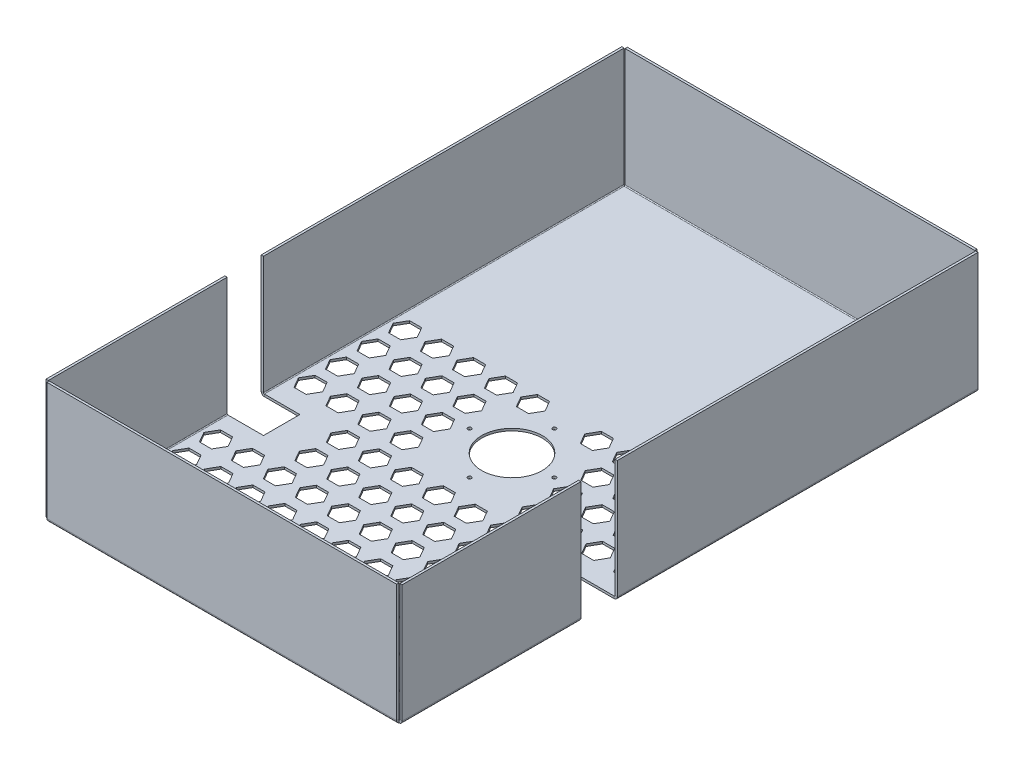
SolidWorks part; units mm, degrees
note: The reader was unsure of these and kept them because the rebuilt part matched: flange length of "Brida de arista1", "Brida de arista2".
ref_plane "Alzado" through (0, 0, 0) normal (0, 0, 1) x (1, 0, 0)
ref_plane "Planta" through (0, 0, 0) normal (0, 1, 0) x (1, 0, 0)
ref_plane "Vista lateral" through (0, 0, 0) normal (1, 0, 0) x (0, 0, -1)
sketch "Croquis1" plane through (0, 0, 0) normal (0, 1, 0) x (1, 0, 0)
  line L0 (-145, -75) -> (-115, -75) construction
  line L1 (-145, 237.5) -> (145, 237.5)
  line L2 (-145, 237.5) -> (-145, -60)
  line L3 (-145, -237.5) -> (145, -237.5)
  line L4 (145, 237.5) -> (145, -60)
  line L5 (-145, 237.5) -> (145, -237.5) construction
  line L6 (-145, -237.5) -> (145, 237.5) construction
  line L7 (0, 35) -> (0, 0) construction
  line L8 (0, 0) -> (-35, 0) construction
  line L9 (-115, -90) -> (-115, -60)
  line L10 (-115, -60) -> (-145, -60)
  line L11 (-115, -90) -> (-145, -90)
  line L12 (-145, -90) -> (-145, -237.5)
  line L13 (115, -90) -> (145, -90)
  line L14 (115, -90) -> (115, -60)
  line L15 (115, -60) -> (145, -60)
  line L16 (145, -90) -> (145, -237.5)
  line L17 (-145, 225.66) -> (-118.6364, 225.66) construction
  line L18 (-118.6364, 225.66) -> (-92.2727, 225.66) construction
  line L19 (-92.2727, 225.66) -> (-65.9091, 225.66) construction
  line L20 (-65.9091, 225.66) -> (-39.5455, 225.66) construction
  line L21 (-39.5455, 225.66) -> (-13.1818, 225.66) construction
  line L22 (-13.1818, 225.66) -> (13.1818, 225.66) construction
  line L23 (13.1818, 225.66) -> (39.5455, 225.66) construction
  line L24 (39.5455, 225.66) -> (65.9091, 225.66) construction
  line L25 (65.9091, 225.66) -> (92.2727, 225.66) construction
  line L26 (92.2727, 225.66) -> (118.6364, 225.66) construction
  line L27 (118.6364, 225.66) -> (145, 225.66) construction
  line L490 (-121.8182, 43.66) -> (-126.8182, 52.3203)
  line L491 (-126.8182, 52.3203) -> (-136.8182, 52.3203)
  line L492 (-136.8182, 52.3203) -> (-141.8182, 43.66)
  line L493 (-141.8182, 43.66) -> (-136.8182, 34.9997)
  line L494 (-136.8182, 34.9997) -> (-126.8182, 34.9997)
  line L495 (-126.8182, 34.9997) -> (-121.8182, 43.66)
  line L496 (-95.4582, 43.66) -> (-100.4582, 52.3203)
  line L497 (-100.4582, 52.3203) -> (-110.4582, 52.3203)
  line L498 (-110.4582, 52.3203) -> (-115.4582, 43.66)
  line L499 (-115.4582, 43.66) -> (-110.4582, 34.9997)
  line L500 (-110.4582, 34.9997) -> (-100.4582, 34.9997)
  line L501 (-100.4582, 34.9997) -> (-95.4582, 43.66)
  line L502 (-69.0982, 43.66) -> (-74.0982, 52.3203)
  line L503 (-74.0982, 52.3203) -> (-84.0982, 52.3203)
  line L504 (-84.0982, 52.3203) -> (-89.0982, 43.66)
  line L505 (-89.0982, 43.66) -> (-84.0982, 34.9997)
  line L506 (-84.0982, 34.9997) -> (-74.0982, 34.9997)
  line L507 (-74.0982, 34.9997) -> (-69.0982, 43.66)
  line L508 (-42.7382, 43.66) -> (-47.7382, 52.3203)
  line L509 (-47.7382, 52.3203) -> (-57.7382, 52.3203)
  line L510 (-57.7382, 52.3203) -> (-62.7382, 43.66)
  line L511 (-62.7382, 43.66) -> (-57.7382, 34.9997)
  line L512 (-57.7382, 34.9997) -> (-47.7382, 34.9997)
  line L513 (-47.7382, 34.9997) -> (-42.7382, 43.66)
  line L514 (-16.3782, 43.66) -> (-21.3782, 52.3203)
  line L515 (-21.3782, 52.3203) -> (-31.3782, 52.3203)
  line L516 (-31.3782, 52.3203) -> (-36.3782, 43.66)
  line L517 (-36.3782, 43.66) -> (-31.3782, 34.9997)
  line L518 (-31.3782, 34.9997) -> (-21.3782, 34.9997)
  line L519 (-21.3782, 34.9997) -> (-16.3782, 43.66)
  line L526 (36.3418, 43.66) -> (31.3418, 52.3203)
  line L527 (31.3418, 52.3203) -> (21.3418, 52.3203)
  line L528 (21.3418, 52.3203) -> (16.3418, 43.66)
  line L529 (16.3418, 43.66) -> (21.3418, 34.9997)
  line L530 (21.3418, 34.9997) -> (31.3418, 34.9997)
  line L531 (31.3418, 34.9997) -> (36.3418, 43.66)
  line L532 (62.7018, 43.66) -> (57.7018, 52.3203)
  line L533 (57.7018, 52.3203) -> (47.7018, 52.3203)
  line L534 (47.7018, 52.3203) -> (42.7018, 43.66)
  line L535 (42.7018, 43.66) -> (47.7018, 34.9997)
  line L536 (47.7018, 34.9997) -> (57.7018, 34.9997)
  line L537 (57.7018, 34.9997) -> (62.7018, 43.66)
  line L538 (89.0618, 43.66) -> (84.0618, 52.3203)
  line L539 (84.0618, 52.3203) -> (74.0618, 52.3203)
  line L540 (74.0618, 52.3203) -> (69.0618, 43.66)
  line L541 (69.0618, 43.66) -> (74.0618, 34.9997)
  line L542 (74.0618, 34.9997) -> (84.0618, 34.9997)
  line L543 (84.0618, 34.9997) -> (89.0618, 43.66)
  line L544 (115.4218, 43.66) -> (110.4218, 52.3203)
  line L545 (110.4218, 52.3203) -> (100.4218, 52.3203)
  line L546 (100.4218, 52.3203) -> (95.4218, 43.66)
  line L547 (95.4218, 43.66) -> (100.4218, 34.9997)
  line L548 (100.4218, 34.9997) -> (110.4218, 34.9997)
  line L549 (110.4218, 34.9997) -> (115.4218, 43.66)
  line L550 (141.7818, 43.66) -> (136.7818, 52.3203)
  line L551 (136.7818, 52.3203) -> (126.7818, 52.3203)
  line L552 (126.7818, 52.3203) -> (121.7818, 43.66)
  line L553 (121.7818, 43.66) -> (126.7818, 34.9997)
  line L554 (126.7818, 34.9997) -> (136.7818, 34.9997)
  line L555 (136.7818, 34.9997) -> (141.7818, 43.66)
  line L556 (-121.8182, 17.66) -> (-126.8182, 26.3203)
  line L557 (-126.8182, 26.3203) -> (-136.8182, 26.3203)
  line L558 (-136.8182, 26.3203) -> (-141.8182, 17.66)
  line L559 (-141.8182, 17.66) -> (-136.8182, 8.9997)
  line L560 (-136.8182, 8.9997) -> (-126.8182, 8.9997)
  line L561 (-126.8182, 8.9997) -> (-121.8182, 17.66)
  line L562 (-95.4582, 17.66) -> (-100.4582, 26.3203)
  line L563 (-100.4582, 26.3203) -> (-110.4582, 26.3203)
  line L564 (-110.4582, 26.3203) -> (-115.4582, 17.66)
  line L565 (-115.4582, 17.66) -> (-110.4582, 8.9997)
  line L566 (-110.4582, 8.9997) -> (-100.4582, 8.9997)
  line L567 (-100.4582, 8.9997) -> (-95.4582, 17.66)
  line L568 (-69.0982, 17.66) -> (-74.0982, 26.3203)
  line L569 (-74.0982, 26.3203) -> (-84.0982, 26.3203)
  line L570 (-84.0982, 26.3203) -> (-89.0982, 17.66)
  line L571 (-89.0982, 17.66) -> (-84.0982, 8.9997)
  line L572 (-84.0982, 8.9997) -> (-74.0982, 8.9997)
  line L573 (-74.0982, 8.9997) -> (-69.0982, 17.66)
  line L574 (-42.7382, 17.66) -> (-47.7382, 26.3203)
  line L575 (-47.7382, 26.3203) -> (-57.7382, 26.3203)
  line L576 (-57.7382, 26.3203) -> (-62.7382, 17.66)
  line L577 (-62.7382, 17.66) -> (-57.7382, 8.9997)
  line L578 (-57.7382, 8.9997) -> (-47.7382, 8.9997)
  line L579 (-47.7382, 8.9997) -> (-42.7382, 17.66)
  line L598 (62.7018, 17.66) -> (57.7018, 26.3203)
  line L599 (57.7018, 26.3203) -> (47.7018, 26.3203)
  line L600 (47.7018, 26.3203) -> (42.7018, 17.66)
  line L601 (42.7018, 17.66) -> (47.7018, 8.9997)
  line L602 (47.7018, 8.9997) -> (57.7018, 8.9997)
  line L603 (57.7018, 8.9997) -> (62.7018, 17.66)
  line L604 (89.0618, 17.66) -> (84.0618, 26.3203)
  line L605 (84.0618, 26.3203) -> (74.0618, 26.3203)
  line L606 (74.0618, 26.3203) -> (69.0618, 17.66)
  line L607 (69.0618, 17.66) -> (74.0618, 8.9997)
  line L608 (74.0618, 8.9997) -> (84.0618, 8.9997)
  line L609 (84.0618, 8.9997) -> (89.0618, 17.66)
  line L610 (115.4218, 17.66) -> (110.4218, 26.3203)
  line L611 (110.4218, 26.3203) -> (100.4218, 26.3203)
  line L612 (100.4218, 26.3203) -> (95.4218, 17.66)
  line L613 (95.4218, 17.66) -> (100.4218, 8.9997)
  line L614 (100.4218, 8.9997) -> (110.4218, 8.9997)
  line L615 (110.4218, 8.9997) -> (115.4218, 17.66)
  line L616 (141.7818, 17.66) -> (136.7818, 26.3203)
  line L617 (136.7818, 26.3203) -> (126.7818, 26.3203)
  line L618 (126.7818, 26.3203) -> (121.7818, 17.66)
  line L619 (121.7818, 17.66) -> (126.7818, 8.9997)
  line L620 (126.7818, 8.9997) -> (136.7818, 8.9997)
  line L621 (136.7818, 8.9997) -> (141.7818, 17.66)
  line L622 (-121.8182, -8.34) -> (-126.8182, 0.3203)
  line L623 (-126.8182, 0.3203) -> (-136.8182, 0.3203)
  line L624 (-136.8182, 0.3203) -> (-141.8182, -8.34)
  line L625 (-141.8182, -8.34) -> (-136.8182, -17.0003)
  line L626 (-136.8182, -17.0003) -> (-126.8182, -17.0003)
  line L627 (-126.8182, -17.0003) -> (-121.8182, -8.34)
  line L628 (-95.4582, -8.34) -> (-100.4582, 0.3203)
  line L629 (-100.4582, 0.3203) -> (-110.4582, 0.3203)
  line L630 (-110.4582, 0.3203) -> (-115.4582, -8.34)
  line L631 (-115.4582, -8.34) -> (-110.4582, -17.0003)
  line L632 (-110.4582, -17.0003) -> (-100.4582, -17.0003)
  line L633 (-100.4582, -17.0003) -> (-95.4582, -8.34)
  line L634 (-69.0982, -8.34) -> (-74.0982, 0.3203)
  line L635 (-74.0982, 0.3203) -> (-84.0982, 0.3203)
  line L636 (-84.0982, 0.3203) -> (-89.0982, -8.34)
  line L637 (-89.0982, -8.34) -> (-84.0982, -17.0003)
  line L638 (-84.0982, -17.0003) -> (-74.0982, -17.0003)
  line L639 (-74.0982, -17.0003) -> (-69.0982, -8.34)
  line L640 (-42.7382, -8.34) -> (-47.7382, 0.3203)
  line L641 (-47.7382, 0.3203) -> (-57.7382, 0.3203)
  line L642 (-57.7382, 0.3203) -> (-62.7382, -8.34)
  line L643 (-62.7382, -8.34) -> (-57.7382, -17.0003)
  line L644 (-57.7382, -17.0003) -> (-47.7382, -17.0003)
  line L645 (-47.7382, -17.0003) -> (-42.7382, -8.34)
  line L664 (62.7018, -8.34) -> (57.7018, 0.3203)
  line L665 (57.7018, 0.3203) -> (47.7018, 0.3203)
  line L666 (47.7018, 0.3203) -> (42.7018, -8.34)
  line L667 (42.7018, -8.34) -> (47.7018, -17.0003)
  line L668 (47.7018, -17.0003) -> (57.7018, -17.0003)
  line L669 (57.7018, -17.0003) -> (62.7018, -8.34)
  line L670 (89.0618, -8.34) -> (84.0618, 0.3203)
  line L671 (84.0618, 0.3203) -> (74.0618, 0.3203)
  line L672 (74.0618, 0.3203) -> (69.0618, -8.34)
  line L673 (69.0618, -8.34) -> (74.0618, -17.0003)
  line L674 (74.0618, -17.0003) -> (84.0618, -17.0003)
  line L675 (84.0618, -17.0003) -> (89.0618, -8.34)
  line L676 (115.4218, -8.34) -> (110.4218, 0.3203)
  line L677 (110.4218, 0.3203) -> (100.4218, 0.3203)
  line L678 (100.4218, 0.3203) -> (95.4218, -8.34)
  line L679 (95.4218, -8.34) -> (100.4218, -17.0003)
  line L680 (100.4218, -17.0003) -> (110.4218, -17.0003)
  line L681 (110.4218, -17.0003) -> (115.4218, -8.34)
  line L682 (141.7818, -8.34) -> (136.7818, 0.3203)
  line L683 (136.7818, 0.3203) -> (126.7818, 0.3203)
  line L684 (126.7818, 0.3203) -> (121.7818, -8.34)
  line L685 (121.7818, -8.34) -> (126.7818, -17.0003)
  line L686 (126.7818, -17.0003) -> (136.7818, -17.0003)
  line L687 (136.7818, -17.0003) -> (141.7818, -8.34)
  line L688 (-121.8182, -34.34) -> (-126.8182, -25.6797)
  line L689 (-126.8182, -25.6797) -> (-136.8182, -25.6797)
  line L690 (-136.8182, -25.6797) -> (-141.8182, -34.34)
  line L691 (-141.8182, -34.34) -> (-136.8182, -43.0003)
  line L692 (-136.8182, -43.0003) -> (-126.8182, -43.0003)
  line L693 (-126.8182, -43.0003) -> (-121.8182, -34.34)
  line L694 (-95.4582, -34.34) -> (-100.4582, -25.6797)
  line L695 (-100.4582, -25.6797) -> (-110.4582, -25.6797)
  line L696 (-110.4582, -25.6797) -> (-115.4582, -34.34)
  line L697 (-115.4582, -34.34) -> (-110.4582, -43.0003)
  line L698 (-110.4582, -43.0003) -> (-100.4582, -43.0003)
  line L699 (-100.4582, -43.0003) -> (-95.4582, -34.34)
  line L700 (-69.0982, -34.34) -> (-74.0982, -25.6797)
  line L701 (-74.0982, -25.6797) -> (-84.0982, -25.6797)
  line L702 (-84.0982, -25.6797) -> (-89.0982, -34.34)
  line L703 (-89.0982, -34.34) -> (-84.0982, -43.0003)
  line L704 (-84.0982, -43.0003) -> (-74.0982, -43.0003)
  line L705 (-74.0982, -43.0003) -> (-69.0982, -34.34)
  line L706 (-42.7382, -34.34) -> (-47.7382, -25.6797)
  line L707 (-47.7382, -25.6797) -> (-57.7382, -25.6797)
  line L708 (-57.7382, -25.6797) -> (-62.7382, -34.34)
  line L709 (-62.7382, -34.34) -> (-57.7382, -43.0003)
  line L710 (-57.7382, -43.0003) -> (-47.7382, -43.0003)
  line L711 (-47.7382, -43.0003) -> (-42.7382, -34.34)
  line L730 (62.7018, -34.34) -> (57.7018, -25.6797)
  line L731 (57.7018, -25.6797) -> (47.7018, -25.6797)
  line L732 (47.7018, -25.6797) -> (42.7018, -34.34)
  line L733 (42.7018, -34.34) -> (47.7018, -43.0003)
  line L734 (47.7018, -43.0003) -> (57.7018, -43.0003)
  line L735 (57.7018, -43.0003) -> (62.7018, -34.34)
  line L736 (89.0618, -34.34) -> (84.0618, -25.6797)
  line L737 (84.0618, -25.6797) -> (74.0618, -25.6797)
  line L738 (74.0618, -25.6797) -> (69.0618, -34.34)
  line L739 (69.0618, -34.34) -> (74.0618, -43.0003)
  line L740 (74.0618, -43.0003) -> (84.0618, -43.0003)
  line L741 (84.0618, -43.0003) -> (89.0618, -34.34)
  line L742 (115.4218, -34.34) -> (110.4218, -25.6797)
  line L743 (110.4218, -25.6797) -> (100.4218, -25.6797)
  line L744 (100.4218, -25.6797) -> (95.4218, -34.34)
  line L745 (95.4218, -34.34) -> (100.4218, -43.0003)
  line L746 (100.4218, -43.0003) -> (110.4218, -43.0003)
  line L747 (110.4218, -43.0003) -> (115.4218, -34.34)
  line L748 (141.7818, -34.34) -> (136.7818, -25.6797)
  line L749 (136.7818, -25.6797) -> (126.7818, -25.6797)
  line L750 (126.7818, -25.6797) -> (121.7818, -34.34)
  line L751 (121.7818, -34.34) -> (126.7818, -43.0003)
  line L752 (126.7818, -43.0003) -> (136.7818, -43.0003)
  line L753 (136.7818, -43.0003) -> (141.7818, -34.34)
  line L766 (-69.0982, -60.34) -> (-74.0982, -51.6797)
  line L767 (-74.0982, -51.6797) -> (-84.0982, -51.6797)
  line L768 (-84.0982, -51.6797) -> (-89.0982, -60.34)
  line L769 (-89.0982, -60.34) -> (-84.0982, -69.0003)
  line L770 (-84.0982, -69.0003) -> (-74.0982, -69.0003)
  line L771 (-74.0982, -69.0003) -> (-69.0982, -60.34)
  line L772 (-42.7382, -60.34) -> (-47.7382, -51.6797)
  line L773 (-47.7382, -51.6797) -> (-57.7382, -51.6797)
  line L774 (-57.7382, -51.6797) -> (-62.7382, -60.34)
  line L775 (-62.7382, -60.34) -> (-57.7382, -69.0003)
  line L776 (-57.7382, -69.0003) -> (-47.7382, -69.0003)
  line L777 (-47.7382, -69.0003) -> (-42.7382, -60.34)
  line L778 (-16.3782, -60.34) -> (-21.3782, -51.6797)
  line L779 (-21.3782, -51.6797) -> (-31.3782, -51.6797)
  line L780 (-31.3782, -51.6797) -> (-36.3782, -60.34)
  line L781 (-36.3782, -60.34) -> (-31.3782, -69.0003)
  line L782 (-31.3782, -69.0003) -> (-21.3782, -69.0003)
  line L783 (-21.3782, -69.0003) -> (-16.3782, -60.34)
  line L784 (9.9818, -60.34) -> (4.9818, -51.6797)
  line L785 (4.9818, -51.6797) -> (-5.0182, -51.6797)
  line L786 (-5.0182, -51.6797) -> (-10.0182, -60.34)
  line L787 (-10.0182, -60.34) -> (-5.0182, -69.0003)
  line L788 (-5.0182, -69.0003) -> (4.9818, -69.0003)
  line L789 (4.9818, -69.0003) -> (9.9818, -60.34)
  line L790 (36.3418, -60.34) -> (31.3418, -51.6797)
  line L791 (31.3418, -51.6797) -> (21.3418, -51.6797)
  line L792 (21.3418, -51.6797) -> (16.3418, -60.34)
  line L793 (16.3418, -60.34) -> (21.3418, -69.0003)
  line L794 (21.3418, -69.0003) -> (31.3418, -69.0003)
  line L795 (31.3418, -69.0003) -> (36.3418, -60.34)
  line L796 (62.7018, -60.34) -> (57.7018, -51.6797)
  line L797 (57.7018, -51.6797) -> (47.7018, -51.6797)
  line L798 (47.7018, -51.6797) -> (42.7018, -60.34)
  line L799 (42.7018, -60.34) -> (47.7018, -69.0003)
  line L800 (47.7018, -69.0003) -> (57.7018, -69.0003)
  line L801 (57.7018, -69.0003) -> (62.7018, -60.34)
  line L802 (89.0618, -60.34) -> (84.0618, -51.6797)
  line L803 (84.0618, -51.6797) -> (74.0618, -51.6797)
  line L804 (74.0618, -51.6797) -> (69.0618, -60.34)
  line L805 (69.0618, -60.34) -> (74.0618, -69.0003)
  line L806 (74.0618, -69.0003) -> (84.0618, -69.0003)
  line L807 (84.0618, -69.0003) -> (89.0618, -60.34)
  line L832 (-69.0982, -86.34) -> (-74.0982, -77.6797)
  line L833 (-74.0982, -77.6797) -> (-84.0982, -77.6797)
  line L834 (-84.0982, -77.6797) -> (-89.0982, -86.34)
  line L835 (-89.0982, -86.34) -> (-84.0982, -95.0003)
  line L836 (-84.0982, -95.0003) -> (-74.0982, -95.0003)
  line L837 (-74.0982, -95.0003) -> (-69.0982, -86.34)
  line L838 (-42.7382, -86.34) -> (-47.7382, -77.6797)
  line L839 (-47.7382, -77.6797) -> (-57.7382, -77.6797)
  line L840 (-57.7382, -77.6797) -> (-62.7382, -86.34)
  line L841 (-62.7382, -86.34) -> (-57.7382, -95.0003)
  line L842 (-57.7382, -95.0003) -> (-47.7382, -95.0003)
  line L843 (-47.7382, -95.0003) -> (-42.7382, -86.34)
  line L844 (-16.3782, -86.34) -> (-21.3782, -77.6797)
  line L845 (-21.3782, -77.6797) -> (-31.3782, -77.6797)
  line L846 (-31.3782, -77.6797) -> (-36.3782, -86.34)
  line L847 (-36.3782, -86.34) -> (-31.3782, -95.0003)
  line L848 (-31.3782, -95.0003) -> (-21.3782, -95.0003)
  line L849 (-21.3782, -95.0003) -> (-16.3782, -86.34)
  line L850 (9.9818, -86.34) -> (4.9818, -77.6797)
  line L851 (4.9818, -77.6797) -> (-5.0182, -77.6797)
  line L852 (-5.0182, -77.6797) -> (-10.0182, -86.34)
  line L853 (-10.0182, -86.34) -> (-5.0182, -95.0003)
  line L854 (-5.0182, -95.0003) -> (4.9818, -95.0003)
  line L855 (4.9818, -95.0003) -> (9.9818, -86.34)
  line L856 (36.3418, -86.34) -> (31.3418, -77.6797)
  line L857 (31.3418, -77.6797) -> (21.3418, -77.6797)
  line L858 (21.3418, -77.6797) -> (16.3418, -86.34)
  line L859 (16.3418, -86.34) -> (21.3418, -95.0003)
  line L860 (21.3418, -95.0003) -> (31.3418, -95.0003)
  line L861 (31.3418, -95.0003) -> (36.3418, -86.34)
  line L862 (62.7018, -86.34) -> (57.7018, -77.6797)
  line L863 (57.7018, -77.6797) -> (47.7018, -77.6797)
  line L864 (47.7018, -77.6797) -> (42.7018, -86.34)
  line L865 (42.7018, -86.34) -> (47.7018, -95.0003)
  line L866 (47.7018, -95.0003) -> (57.7018, -95.0003)
  line L867 (57.7018, -95.0003) -> (62.7018, -86.34)
  line L868 (89.0618, -86.34) -> (84.0618, -77.6797)
  line L869 (84.0618, -77.6797) -> (74.0618, -77.6797)
  line L870 (74.0618, -77.6797) -> (69.0618, -86.34)
  line L871 (69.0618, -86.34) -> (74.0618, -95.0003)
  line L872 (74.0618, -95.0003) -> (84.0618, -95.0003)
  line L873 (84.0618, -95.0003) -> (89.0618, -86.34)
  line L886 (-121.8182, -112.34) -> (-126.8182, -103.6797)
  line L887 (-126.8182, -103.6797) -> (-136.8182, -103.6797)
  line L888 (-136.8182, -103.6797) -> (-141.8182, -112.34)
  line L889 (-141.8182, -112.34) -> (-136.8182, -121.0003)
  line L890 (-136.8182, -121.0003) -> (-126.8182, -121.0003)
  line L891 (-126.8182, -121.0003) -> (-121.8182, -112.34)
  line L892 (-95.4582, -112.34) -> (-100.4582, -103.6797)
  line L893 (-100.4582, -103.6797) -> (-110.4582, -103.6797)
  line L894 (-110.4582, -103.6797) -> (-115.4582, -112.34)
  line L895 (-115.4582, -112.34) -> (-110.4582, -121.0003)
  line L896 (-110.4582, -121.0003) -> (-100.4582, -121.0003)
  line L897 (-100.4582, -121.0003) -> (-95.4582, -112.34)
  line L898 (-69.0982, -112.34) -> (-74.0982, -103.6797)
  line L899 (-74.0982, -103.6797) -> (-84.0982, -103.6797)
  line L900 (-84.0982, -103.6797) -> (-89.0982, -112.34)
  line L901 (-89.0982, -112.34) -> (-84.0982, -121.0003)
  line L902 (-84.0982, -121.0003) -> (-74.0982, -121.0003)
  line L903 (-74.0982, -121.0003) -> (-69.0982, -112.34)
  line L904 (-42.7382, -112.34) -> (-47.7382, -103.6797)
  line L905 (-47.7382, -103.6797) -> (-57.7382, -103.6797)
  line L906 (-57.7382, -103.6797) -> (-62.7382, -112.34)
  line L907 (-62.7382, -112.34) -> (-57.7382, -121.0003)
  line L908 (-57.7382, -121.0003) -> (-47.7382, -121.0003)
  line L909 (-47.7382, -121.0003) -> (-42.7382, -112.34)
  line L910 (-16.3782, -112.34) -> (-21.3782, -103.6797)
  line L911 (-21.3782, -103.6797) -> (-31.3782, -103.6797)
  line L912 (-31.3782, -103.6797) -> (-36.3782, -112.34)
  line L913 (-36.3782, -112.34) -> (-31.3782, -121.0003)
  line L914 (-31.3782, -121.0003) -> (-21.3782, -121.0003)
  line L915 (-21.3782, -121.0003) -> (-16.3782, -112.34)
  line L916 (9.9818, -112.34) -> (4.9818, -103.6797)
  line L917 (4.9818, -103.6797) -> (-5.0182, -103.6797)
  line L918 (-5.0182, -103.6797) -> (-10.0182, -112.34)
  line L919 (-10.0182, -112.34) -> (-5.0182, -121.0003)
  line L920 (-5.0182, -121.0003) -> (4.9818, -121.0003)
  line L921 (4.9818, -121.0003) -> (9.9818, -112.34)
  line L922 (36.3418, -112.34) -> (31.3418, -103.6797)
  line L923 (31.3418, -103.6797) -> (21.3418, -103.6797)
  line L924 (21.3418, -103.6797) -> (16.3418, -112.34)
  line L925 (16.3418, -112.34) -> (21.3418, -121.0003)
  line L926 (21.3418, -121.0003) -> (31.3418, -121.0003)
  line L927 (31.3418, -121.0003) -> (36.3418, -112.34)
  line L928 (62.7018, -112.34) -> (57.7018, -103.6797)
  line L929 (57.7018, -103.6797) -> (47.7018, -103.6797)
  line L930 (47.7018, -103.6797) -> (42.7018, -112.34)
  line L931 (42.7018, -112.34) -> (47.7018, -121.0003)
  line L932 (47.7018, -121.0003) -> (57.7018, -121.0003)
  line L933 (57.7018, -121.0003) -> (62.7018, -112.34)
  line L934 (89.0618, -112.34) -> (84.0618, -103.6797)
  line L935 (84.0618, -103.6797) -> (74.0618, -103.6797)
  line L936 (74.0618, -103.6797) -> (69.0618, -112.34)
  line L937 (69.0618, -112.34) -> (74.0618, -121.0003)
  line L938 (74.0618, -121.0003) -> (84.0618, -121.0003)
  line L939 (84.0618, -121.0003) -> (89.0618, -112.34)
  line L940 (115.4218, -112.34) -> (110.4218, -103.6797)
  line L941 (110.4218, -103.6797) -> (100.4218, -103.6797)
  line L942 (100.4218, -103.6797) -> (95.4218, -112.34)
  line L943 (95.4218, -112.34) -> (100.4218, -121.0003)
  line L944 (100.4218, -121.0003) -> (110.4218, -121.0003)
  line L945 (110.4218, -121.0003) -> (115.4218, -112.34)
  line L946 (141.7818, -112.34) -> (136.7818, -103.6797)
  line L947 (136.7818, -103.6797) -> (126.7818, -103.6797)
  line L948 (126.7818, -103.6797) -> (121.7818, -112.34)
  line L949 (121.7818, -112.34) -> (126.7818, -121.0003)
  line L950 (126.7818, -121.0003) -> (136.7818, -121.0003)
  line L951 (136.7818, -121.0003) -> (141.7818, -112.34)
  line L952 (-121.8182, -138.34) -> (-126.8182, -129.6797)
  line L953 (-126.8182, -129.6797) -> (-136.8182, -129.6797)
  line L954 (-136.8182, -129.6797) -> (-141.8182, -138.34)
  line L955 (-141.8182, -138.34) -> (-136.8182, -147.0003)
  line L956 (-136.8182, -147.0003) -> (-126.8182, -147.0003)
  line L957 (-126.8182, -147.0003) -> (-121.8182, -138.34)
  line L958 (-95.4582, -138.34) -> (-100.4582, -129.6797)
  line L959 (-100.4582, -129.6797) -> (-110.4582, -129.6797)
  line L960 (-110.4582, -129.6797) -> (-115.4582, -138.34)
  line L961 (-115.4582, -138.34) -> (-110.4582, -147.0003)
  line L962 (-110.4582, -147.0003) -> (-100.4582, -147.0003)
  line L963 (-100.4582, -147.0003) -> (-95.4582, -138.34)
  line L964 (-69.0982, -138.34) -> (-74.0982, -129.6797)
  line L965 (-74.0982, -129.6797) -> (-84.0982, -129.6797)
  line L966 (-84.0982, -129.6797) -> (-89.0982, -138.34)
  line L967 (-89.0982, -138.34) -> (-84.0982, -147.0003)
  line L968 (-84.0982, -147.0003) -> (-74.0982, -147.0003)
  line L969 (-74.0982, -147.0003) -> (-69.0982, -138.34)
  line L970 (-42.7382, -138.34) -> (-47.7382, -129.6797)
  line L971 (-47.7382, -129.6797) -> (-57.7382, -129.6797)
  line L972 (-57.7382, -129.6797) -> (-62.7382, -138.34)
  line L973 (-62.7382, -138.34) -> (-57.7382, -147.0003)
  line L974 (-57.7382, -147.0003) -> (-47.7382, -147.0003)
  line L975 (-47.7382, -147.0003) -> (-42.7382, -138.34)
  line L976 (-16.3782, -138.34) -> (-21.3782, -129.6797)
  line L977 (-21.3782, -129.6797) -> (-31.3782, -129.6797)
  line L978 (-31.3782, -129.6797) -> (-36.3782, -138.34)
  line L979 (-36.3782, -138.34) -> (-31.3782, -147.0003)
  line L980 (-31.3782, -147.0003) -> (-21.3782, -147.0003)
  line L981 (-21.3782, -147.0003) -> (-16.3782, -138.34)
  line L982 (9.9818, -138.34) -> (4.9818, -129.6797)
  line L983 (4.9818, -129.6797) -> (-5.0182, -129.6797)
  line L984 (-5.0182, -129.6797) -> (-10.0182, -138.34)
  line L985 (-10.0182, -138.34) -> (-5.0182, -147.0003)
  line L986 (-5.0182, -147.0003) -> (4.9818, -147.0003)
  line L987 (4.9818, -147.0003) -> (9.9818, -138.34)
  line L988 (36.3418, -138.34) -> (31.3418, -129.6797)
  line L989 (31.3418, -129.6797) -> (21.3418, -129.6797)
  line L990 (21.3418, -129.6797) -> (16.3418, -138.34)
  line L991 (16.3418, -138.34) -> (21.3418, -147.0003)
  line L992 (21.3418, -147.0003) -> (31.3418, -147.0003)
  line L993 (31.3418, -147.0003) -> (36.3418, -138.34)
  line L994 (62.7018, -138.34) -> (57.7018, -129.6797)
  line L995 (57.7018, -129.6797) -> (47.7018, -129.6797)
  line L996 (47.7018, -129.6797) -> (42.7018, -138.34)
  line L997 (42.7018, -138.34) -> (47.7018, -147.0003)
  line L998 (47.7018, -147.0003) -> (57.7018, -147.0003)
  line L999 (57.7018, -147.0003) -> (62.7018, -138.34)
  line L1000 (89.0618, -138.34) -> (84.0618, -129.6797)
  line L1001 (84.0618, -129.6797) -> (74.0618, -129.6797)
  line L1002 (74.0618, -129.6797) -> (69.0618, -138.34)
  line L1003 (69.0618, -138.34) -> (74.0618, -147.0003)
  line L1004 (74.0618, -147.0003) -> (84.0618, -147.0003)
  line L1005 (84.0618, -147.0003) -> (89.0618, -138.34)
  line L1006 (115.4218, -138.34) -> (110.4218, -129.6797)
  line L1007 (110.4218, -129.6797) -> (100.4218, -129.6797)
  line L1008 (100.4218, -129.6797) -> (95.4218, -138.34)
  line L1009 (95.4218, -138.34) -> (100.4218, -147.0003)
  line L1010 (100.4218, -147.0003) -> (110.4218, -147.0003)
  line L1011 (110.4218, -147.0003) -> (115.4218, -138.34)
  line L1012 (141.7818, -138.34) -> (136.7818, -129.6797)
  line L1013 (136.7818, -129.6797) -> (126.7818, -129.6797)
  line L1014 (126.7818, -129.6797) -> (121.7818, -138.34)
  line L1015 (121.7818, -138.34) -> (126.7818, -147.0003)
  line L1016 (126.7818, -147.0003) -> (136.7818, -147.0003)
  line L1017 (136.7818, -147.0003) -> (141.7818, -138.34)
  line L1018 (-121.8182, -164.34) -> (-126.8182, -155.6797)
  line L1019 (-126.8182, -155.6797) -> (-136.8182, -155.6797)
  line L1020 (-136.8182, -155.6797) -> (-141.8182, -164.34)
  line L1021 (-141.8182, -164.34) -> (-136.8182, -173.0003)
  line L1022 (-136.8182, -173.0003) -> (-126.8182, -173.0003)
  line L1023 (-126.8182, -173.0003) -> (-121.8182, -164.34)
  line L1024 (-95.4582, -164.34) -> (-100.4582, -155.6797)
  line L1025 (-100.4582, -155.6797) -> (-110.4582, -155.6797)
  line L1026 (-110.4582, -155.6797) -> (-115.4582, -164.34)
  line L1027 (-115.4582, -164.34) -> (-110.4582, -173.0003)
  line L1028 (-110.4582, -173.0003) -> (-100.4582, -173.0003)
  line L1029 (-100.4582, -173.0003) -> (-95.4582, -164.34)
  line L1030 (-69.0982, -164.34) -> (-74.0982, -155.6797)
  line L1031 (-74.0982, -155.6797) -> (-84.0982, -155.6797)
  line L1032 (-84.0982, -155.6797) -> (-89.0982, -164.34)
  line L1033 (-89.0982, -164.34) -> (-84.0982, -173.0003)
  line L1034 (-84.0982, -173.0003) -> (-74.0982, -173.0003)
  line L1035 (-74.0982, -173.0003) -> (-69.0982, -164.34)
  line L1036 (-42.7382, -164.34) -> (-47.7382, -155.6797)
  line L1037 (-47.7382, -155.6797) -> (-57.7382, -155.6797)
  line L1038 (-57.7382, -155.6797) -> (-62.7382, -164.34)
  line L1039 (-62.7382, -164.34) -> (-57.7382, -173.0003)
  line L1040 (-57.7382, -173.0003) -> (-47.7382, -173.0003)
  line L1041 (-47.7382, -173.0003) -> (-42.7382, -164.34)
  line L1042 (-16.3782, -164.34) -> (-21.3782, -155.6797)
  line L1043 (-21.3782, -155.6797) -> (-31.3782, -155.6797)
  line L1044 (-31.3782, -155.6797) -> (-36.3782, -164.34)
  line L1045 (-36.3782, -164.34) -> (-31.3782, -173.0003)
  line L1046 (-31.3782, -173.0003) -> (-21.3782, -173.0003)
  line L1047 (-21.3782, -173.0003) -> (-16.3782, -164.34)
  line L1048 (9.9818, -164.34) -> (4.9818, -155.6797)
  line L1049 (4.9818, -155.6797) -> (-5.0182, -155.6797)
  line L1050 (-5.0182, -155.6797) -> (-10.0182, -164.34)
  line L1051 (-10.0182, -164.34) -> (-5.0182, -173.0003)
  line L1052 (-5.0182, -173.0003) -> (4.9818, -173.0003)
  line L1053 (4.9818, -173.0003) -> (9.9818, -164.34)
  line L1054 (36.3418, -164.34) -> (31.3418, -155.6797)
  line L1055 (31.3418, -155.6797) -> (21.3418, -155.6797)
  line L1056 (21.3418, -155.6797) -> (16.3418, -164.34)
  line L1057 (16.3418, -164.34) -> (21.3418, -173.0003)
  line L1058 (21.3418, -173.0003) -> (31.3418, -173.0003)
  line L1059 (31.3418, -173.0003) -> (36.3418, -164.34)
  line L1060 (62.7018, -164.34) -> (57.7018, -155.6797)
  line L1061 (57.7018, -155.6797) -> (47.7018, -155.6797)
  line L1062 (47.7018, -155.6797) -> (42.7018, -164.34)
  line L1063 (42.7018, -164.34) -> (47.7018, -173.0003)
  line L1064 (47.7018, -173.0003) -> (57.7018, -173.0003)
  line L1065 (57.7018, -173.0003) -> (62.7018, -164.34)
  line L1066 (89.0618, -164.34) -> (84.0618, -155.6797)
  line L1067 (84.0618, -155.6797) -> (74.0618, -155.6797)
  line L1068 (74.0618, -155.6797) -> (69.0618, -164.34)
  line L1069 (69.0618, -164.34) -> (74.0618, -173.0003)
  line L1070 (74.0618, -173.0003) -> (84.0618, -173.0003)
  line L1071 (84.0618, -173.0003) -> (89.0618, -164.34)
  line L1072 (115.4218, -164.34) -> (110.4218, -155.6797)
  line L1073 (110.4218, -155.6797) -> (100.4218, -155.6797)
  line L1074 (100.4218, -155.6797) -> (95.4218, -164.34)
  line L1075 (95.4218, -164.34) -> (100.4218, -173.0003)
  line L1076 (100.4218, -173.0003) -> (110.4218, -173.0003)
  line L1077 (110.4218, -173.0003) -> (115.4218, -164.34)
  line L1078 (141.7818, -164.34) -> (136.7818, -155.6797)
  line L1079 (136.7818, -155.6797) -> (126.7818, -155.6797)
  line L1080 (126.7818, -155.6797) -> (121.7818, -164.34)
  line L1081 (121.7818, -164.34) -> (126.7818, -173.0003)
  line L1082 (126.7818, -173.0003) -> (136.7818, -173.0003)
  line L1083 (136.7818, -173.0003) -> (141.7818, -164.34)
  line L1084 (-121.8182, -190.34) -> (-126.8182, -181.6797)
  line L1085 (-126.8182, -181.6797) -> (-136.8182, -181.6797)
  line L1086 (-136.8182, -181.6797) -> (-141.8182, -190.34)
  line L1087 (-141.8182, -190.34) -> (-136.8182, -199.0003)
  line L1088 (-136.8182, -199.0003) -> (-126.8182, -199.0003)
  line L1089 (-126.8182, -199.0003) -> (-121.8182, -190.34)
  line L1090 (-95.4582, -190.34) -> (-100.4582, -181.6797)
  line L1091 (-100.4582, -181.6797) -> (-110.4582, -181.6797)
  line L1092 (-110.4582, -181.6797) -> (-115.4582, -190.34)
  line L1093 (-115.4582, -190.34) -> (-110.4582, -199.0003)
  line L1094 (-110.4582, -199.0003) -> (-100.4582, -199.0003)
  line L1095 (-100.4582, -199.0003) -> (-95.4582, -190.34)
  line L1096 (-69.0982, -190.34) -> (-74.0982, -181.6797)
  line L1097 (-74.0982, -181.6797) -> (-84.0982, -181.6797)
  line L1098 (-84.0982, -181.6797) -> (-89.0982, -190.34)
  line L1099 (-89.0982, -190.34) -> (-84.0982, -199.0003)
  line L1100 (-84.0982, -199.0003) -> (-74.0982, -199.0003)
  line L1101 (-74.0982, -199.0003) -> (-69.0982, -190.34)
  line L1102 (-42.7382, -190.34) -> (-47.7382, -181.6797)
  line L1103 (-47.7382, -181.6797) -> (-57.7382, -181.6797)
  line L1104 (-57.7382, -181.6797) -> (-62.7382, -190.34)
  line L1105 (-62.7382, -190.34) -> (-57.7382, -199.0003)
  line L1106 (-57.7382, -199.0003) -> (-47.7382, -199.0003)
  line L1107 (-47.7382, -199.0003) -> (-42.7382, -190.34)
  line L1108 (-16.3782, -190.34) -> (-21.3782, -181.6797)
  line L1109 (-21.3782, -181.6797) -> (-31.3782, -181.6797)
  line L1110 (-31.3782, -181.6797) -> (-36.3782, -190.34)
  line L1111 (-36.3782, -190.34) -> (-31.3782, -199.0003)
  line L1112 (-31.3782, -199.0003) -> (-21.3782, -199.0003)
  line L1113 (-21.3782, -199.0003) -> (-16.3782, -190.34)
  line L1114 (9.9818, -190.34) -> (4.9818, -181.6797)
  line L1115 (4.9818, -181.6797) -> (-5.0182, -181.6797)
  line L1116 (-5.0182, -181.6797) -> (-10.0182, -190.34)
  line L1117 (-10.0182, -190.34) -> (-5.0182, -199.0003)
  line L1118 (-5.0182, -199.0003) -> (4.9818, -199.0003)
  line L1119 (4.9818, -199.0003) -> (9.9818, -190.34)
  line L1120 (36.3418, -190.34) -> (31.3418, -181.6797)
  line L1121 (31.3418, -181.6797) -> (21.3418, -181.6797)
  line L1122 (21.3418, -181.6797) -> (16.3418, -190.34)
  line L1123 (16.3418, -190.34) -> (21.3418, -199.0003)
  line L1124 (21.3418, -199.0003) -> (31.3418, -199.0003)
  line L1125 (31.3418, -199.0003) -> (36.3418, -190.34)
  line L1126 (62.7018, -190.34) -> (57.7018, -181.6797)
  line L1127 (57.7018, -181.6797) -> (47.7018, -181.6797)
  line L1128 (47.7018, -181.6797) -> (42.7018, -190.34)
  line L1129 (42.7018, -190.34) -> (47.7018, -199.0003)
  line L1130 (47.7018, -199.0003) -> (57.7018, -199.0003)
  line L1131 (57.7018, -199.0003) -> (62.7018, -190.34)
  line L1132 (89.0618, -190.34) -> (84.0618, -181.6797)
  line L1133 (84.0618, -181.6797) -> (74.0618, -181.6797)
  line L1134 (74.0618, -181.6797) -> (69.0618, -190.34)
  line L1135 (69.0618, -190.34) -> (74.0618, -199.0003)
  line L1136 (74.0618, -199.0003) -> (84.0618, -199.0003)
  line L1137 (84.0618, -199.0003) -> (89.0618, -190.34)
  line L1138 (115.4218, -190.34) -> (110.4218, -181.6797)
  line L1139 (110.4218, -181.6797) -> (100.4218, -181.6797)
  line L1140 (100.4218, -181.6797) -> (95.4218, -190.34)
  line L1141 (95.4218, -190.34) -> (100.4218, -199.0003)
  line L1142 (100.4218, -199.0003) -> (110.4218, -199.0003)
  line L1143 (110.4218, -199.0003) -> (115.4218, -190.34)
  line L1144 (141.7818, -190.34) -> (136.7818, -181.6797)
  line L1145 (136.7818, -181.6797) -> (126.7818, -181.6797)
  line L1146 (126.7818, -181.6797) -> (121.7818, -190.34)
  line L1147 (121.7818, -190.34) -> (126.7818, -199.0003)
  line L1148 (126.7818, -199.0003) -> (136.7818, -199.0003)
  line L1149 (136.7818, -199.0003) -> (141.7818, -190.34)
  line L1150 (-121.8182, -216.34) -> (-126.8182, -207.6797)
  line L1151 (-126.8182, -207.6797) -> (-136.8182, -207.6797)
  line L1152 (-136.8182, -207.6797) -> (-141.8182, -216.34)
  line L1153 (-141.8182, -216.34) -> (-136.8182, -225.0003)
  line L1154 (-136.8182, -225.0003) -> (-126.8182, -225.0003)
  line L1155 (-126.8182, -225.0003) -> (-121.8182, -216.34)
  line L1156 (-95.4582, -216.34) -> (-100.4582, -207.6797)
  line L1157 (-100.4582, -207.6797) -> (-110.4582, -207.6797)
  line L1158 (-110.4582, -207.6797) -> (-115.4582, -216.34)
  line L1159 (-115.4582, -216.34) -> (-110.4582, -225.0003)
  line L1160 (-110.4582, -225.0003) -> (-100.4582, -225.0003)
  line L1161 (-100.4582, -225.0003) -> (-95.4582, -216.34)
  line L1162 (-69.0982, -216.34) -> (-74.0982, -207.6797)
  line L1163 (-74.0982, -207.6797) -> (-84.0982, -207.6797)
  line L1164 (-84.0982, -207.6797) -> (-89.0982, -216.34)
  line L1165 (-89.0982, -216.34) -> (-84.0982, -225.0003)
  line L1166 (-84.0982, -225.0003) -> (-74.0982, -225.0003)
  line L1167 (-74.0982, -225.0003) -> (-69.0982, -216.34)
  line L1168 (-42.7382, -216.34) -> (-47.7382, -207.6797)
  line L1169 (-47.7382, -207.6797) -> (-57.7382, -207.6797)
  line L1170 (-57.7382, -207.6797) -> (-62.7382, -216.34)
  line L1171 (-62.7382, -216.34) -> (-57.7382, -225.0003)
  line L1172 (-57.7382, -225.0003) -> (-47.7382, -225.0003)
  line L1173 (-47.7382, -225.0003) -> (-42.7382, -216.34)
  line L1174 (-16.3782, -216.34) -> (-21.3782, -207.6797)
  line L1175 (-21.3782, -207.6797) -> (-31.3782, -207.6797)
  line L1176 (-31.3782, -207.6797) -> (-36.3782, -216.34)
  line L1177 (-36.3782, -216.34) -> (-31.3782, -225.0003)
  line L1178 (-31.3782, -225.0003) -> (-21.3782, -225.0003)
  line L1179 (-21.3782, -225.0003) -> (-16.3782, -216.34)
  line L1180 (9.9818, -216.34) -> (4.9818, -207.6797)
  line L1181 (4.9818, -207.6797) -> (-5.0182, -207.6797)
  line L1182 (-5.0182, -207.6797) -> (-10.0182, -216.34)
  line L1183 (-10.0182, -216.34) -> (-5.0182, -225.0003)
  line L1184 (-5.0182, -225.0003) -> (4.9818, -225.0003)
  line L1185 (4.9818, -225.0003) -> (9.9818, -216.34)
  line L1186 (36.3418, -216.34) -> (31.3418, -207.6797)
  line L1187 (31.3418, -207.6797) -> (21.3418, -207.6797)
  line L1188 (21.3418, -207.6797) -> (16.3418, -216.34)
  line L1189 (16.3418, -216.34) -> (21.3418, -225.0003)
  line L1190 (21.3418, -225.0003) -> (31.3418, -225.0003)
  line L1191 (31.3418, -225.0003) -> (36.3418, -216.34)
  line L1192 (62.7018, -216.34) -> (57.7018, -207.6797)
  line L1193 (57.7018, -207.6797) -> (47.7018, -207.6797)
  line L1194 (47.7018, -207.6797) -> (42.7018, -216.34)
  line L1195 (42.7018, -216.34) -> (47.7018, -225.0003)
  line L1196 (47.7018, -225.0003) -> (57.7018, -225.0003)
  line L1197 (57.7018, -225.0003) -> (62.7018, -216.34)
  line L1198 (89.0618, -216.34) -> (84.0618, -207.6797)
  line L1199 (84.0618, -207.6797) -> (74.0618, -207.6797)
  line L1200 (74.0618, -207.6797) -> (69.0618, -216.34)
  line L1201 (69.0618, -216.34) -> (74.0618, -225.0003)
  line L1202 (74.0618, -225.0003) -> (84.0618, -225.0003)
  line L1203 (84.0618, -225.0003) -> (89.0618, -216.34)
  line L1204 (115.4218, -216.34) -> (110.4218, -207.6797)
  line L1205 (110.4218, -207.6797) -> (100.4218, -207.6797)
  line L1206 (100.4218, -207.6797) -> (95.4218, -216.34)
  line L1207 (95.4218, -216.34) -> (100.4218, -225.0003)
  line L1208 (100.4218, -225.0003) -> (110.4218, -225.0003)
  line L1209 (110.4218, -225.0003) -> (115.4218, -216.34)
  line L1210 (141.7818, -216.34) -> (136.7818, -207.6797)
  line L1211 (136.7818, -207.6797) -> (126.7818, -207.6797)
  line L1212 (126.7818, -207.6797) -> (121.7818, -216.34)
  line L1213 (121.7818, -216.34) -> (126.7818, -225.0003)
  line L1214 (126.7818, -225.0003) -> (136.7818, -225.0003)
  line L1215 (136.7818, -225.0003) -> (141.7818, -216.34)
  circle A0 centre (0, 35) radius 1.5
  circle A1 centre (-35, 0) radius 1.5
  circle A2 centre (0, -35) radius 1.5
  circle A3 centre (35, 0) radius 1.5
  point P0 (0, 0)
  point P14 (-115, -75)
  dimension "D8" = 3
  dimension "D1" = 290
  dimension "D2" = 475
  dimension "D3" = 30
  dimension "D4" = 30
  dimension "D5" = 60
  dimension "D6" = 35
  dimension "D7" = 35
  dimension "D10" = 11.84
base flange "Brida base2" sketch "Croquis1" thickness 1.9 reverse thickness direction no parameters "D1"=0.7366
sketch "Croquis3" plane through (0, 0, 0) normal (0, 1, 0) x (1, 0, 0)
  circle A0 centre (0, 0) radius 25
  dimension "D1" = 50
extrude "Cortar-Extruir1" cut sketch "Croquis3" against normal blind 10 normal cut yes
edge flange "Brida de arista1" sketch "Croquis16" flange profiles "Croquis16", "Croquis17", "Croquis19", "Croquis21" flange angle 90 flange length 100 flange position material outside bend radius 0.7366 thickness 1.9 relief rectangular parameters "D6"=10, "D8"=3
sketch "Croquis16" plane through (145, 0, 0) normal (1, 0, 0) x (0, 0, -1)
  line L0 (-60, 0) -> (237.5, 0) construction
  line L1 (-60, 0) -> (237.5, 0)
  line L2 (-60, 0) -> (-60, 98.1)
  line L3 (-60, 98.1) -> (237.5, 98.1)
  line L4 (237.5, 98.1) -> (237.5, 0)
sketch "Croquis17" plane through (-145, 0, 0) normal (-1, 0, 0) x (0, 0, 1)
  line L0 (-237.5, 0) -> (60, 0) construction
  line L1 (-237.5, 0) -> (60, 0)
  line L2 (-237.5, 0) -> (-237.5, 98.1)
  line L3 (-237.5, 98.1) -> (60, 98.1)
  line L4 (60, 98.1) -> (60, 0)
sketch "Croquis19" plane through (-145, 0, 0) normal (-1, 0, 0) x (0, 0, 1)
  line L0 (90, 0) -> (237.5, 0) construction
  line L1 (90, 0) -> (237.5, 0)
  line L2 (90, 0) -> (90, 98.1)
  line L3 (90, 98.1) -> (237.5, 98.1)
  line L4 (237.5, 98.1) -> (237.5, 0)
sketch "Croquis21" plane through (145, 0, 0) normal (1, 0, 0) x (0, 0, -1)
  line L0 (-237.5, 0) -> (-90, 0) construction
  line L1 (-237.5, 0) -> (-90, 0)
  line L2 (-237.5, 0) -> (-237.5, 98.1)
  line L3 (-237.5, 98.1) -> (-90, 98.1)
  line L4 (-90, 98.1) -> (-90, 0)
bend "Pliegue de arista1" bend radius 0.7366 bend angle 90 parameters "D5"=1
bend "Pliegue de arista2" bend radius 0.7366 bend angle 90 parameters "D5"=2
bend "Pliegue de arista3" bend radius 0.7366 bend angle 90 parameters "D5"=5
bend "Pliegue de arista4" bend radius 0.7366 bend angle 90 parameters "D5"=6
ref_plane "Plano1" through (-144.2634, 0, -237.5) normal (-1, 0, 0) x (0, 0, 1)
edge flange "Brida de arista2" sketch "Croquis27" flange profiles "Croquis27", "Croquis28" flange angle 90 flange length 100 flange position material outside bend radius 0.7366 thickness 1.9 relief none parameters "D6"=10, "D8"=3
sketch "Croquis27" plane through (0, 0, -237.5) normal (0, 0, -1) x (-1, 0, 0)
  line L0 (-144.2634, 0) -> (144.2634, 0) construction
  line L1 (-144.2634, 0) -> (144.2634, 0)
  line L2 (-144.2634, 0) -> (-144.2634, 98.1)
  line L3 (-144.2634, 98.1) -> (144.2634, 98.1)
  line L4 (144.2634, 98.1) -> (144.2634, 0)
sketch "Croquis28" plane through (0, 0, 237.5) normal (0, 0, 1) x (1, 0, 0)
  line L0 (-144.2634, 0) -> (144.2634, 0) construction
  line L1 (-144.2634, 0) -> (144.2634, 0)
  line L2 (-144.2634, 0) -> (-144.2634, 98.1)
  line L3 (-144.2634, 98.1) -> (144.2634, 98.1)
  line L4 (144.2634, 98.1) -> (144.2634, 0)
bend "Pliegue de arista5" bend radius 0.7366 bend angle 90 parameters "D5"=7
bend "Pliegue de arista6" bend radius 0.7366 bend angle 90 parameters "D5"=8
sketch "Líneas de pliegue3" [suppressed] plane through (0, 0, 0) normal (0, 1, 0) x (1, 0, 0)
sketch "Cuadro delimitador3" [suppressed] plane through (0, 0, 0) normal (0, 1, 0) x (1, 0, 0)
sheet metal parameters "Chapa metálica9" thickness 1.9 parameters "D1"=0.7366
flat pattern "Chapa desplegada9" [suppressed]
sketch "Líneas de pliegue4" plane through (0, 0, 0) normal (0, 1, 0) x (1, 0, 0)
sketch3d "Cuadro delimitador4" [suppressed]
  line L0 (150, 237.5, 0) -> (150, -237.5, 0) construction
  line L1 (-150, 237.5, 0) -> (-150, -237.5, 0) construction
  line L2 (150, 237.5, 0) -> (-150, 237.5, 0) construction
  line L3 (150, -237.5, 0) -> (-150, -237.5, 0) construction
sheet metal parameters "Chapa metálica10" thickness 1.9 parameters "D1"=0.7366
flat pattern "Chapa desplegada9"
sketch "Líneas de pliegue4" plane through (0, 0, 0) normal (0, 1, 0) x (1, 0, 0)
sketch3d "Cuadro delimitador4" [suppressed]
  line L0 (-150, 237.5, 0) -> (-150, -237.5, 0) construction
  line L1 (150, 237.5, 0) -> (150, -237.5, 0) construction
  line L2 (-150, 237.5, 0) -> (150, 237.5, 0) construction
  line L3 (-150, -237.5, 0) -> (150, -237.5, 0) construction
sheet metal parameters "Chapa metálica11" thickness 1.9 parameters "D1"=0.7366
flat pattern "Chapa desplegada9"
sketch "Líneas de pliegue4" plane through (0, 0, 0) normal (0, 1, 0) x (1, 0, 0)
  line L0 (-145.5881, 237.5) -> (-145.5881, -60) construction
  line L1 (145.5881, -60) -> (145.5881, 237.5) construction
  line L2 (-145.5881, 237.5) -> (-145.5881, -60) construction
  line L3 (145.5881, -60) -> (145.5881, 237.5) construction
  line L4 (145.5881, -237.5) -> (145.5881, -90) construction
  line L5 (-145.5881, -90) -> (-145.5881, -237.5) construction
  line L6 (145.5881, -237.5) -> (145.5881, -90) construction
  line L7 (-145.5881, -90) -> (-145.5881, -237.5) construction
sketch3d "Cuadro delimitador4" [suppressed]
  line L0 (244.2761, -237.5, 0) -> (-244.2761, -237.5, 0) construction
  line L1 (244.2761, 237.5, 0) -> (-244.2761, 237.5, 0) construction
  line L2 (244.2761, -237.5, 0) -> (244.2761, 237.5, 0) construction
  line L3 (-244.2761, -237.5, 0) -> (-244.2761, 237.5, 0) construction
bend of the flat pattern "Aplanar-<Pliegue de arista1>1"
bend of the flat pattern "Aplanar-<Pliegue de arista2>1"
bend of the flat pattern "Aplanar-<Pliegue de arista3>1"
bend of the flat pattern "Aplanar-<Pliegue de arista4>1"
sheet metal parameters "Chapa metálica12" thickness 1.9 parameters "D1"=0.7366
flat pattern "Chapa desplegada9"
sketch "Líneas de pliegue4" plane through (0, 0, 0) normal (0, 1, 0) x (1, 0, 0)
  line L0 (-145.5881, 237.5) -> (-145.5881, -60) construction
  line L1 (145.5881, -60) -> (145.5881, 237.5) construction
  line L2 (-145.5881, 237.5) -> (-145.5881, -60) construction
  line L3 (145.5881, -60) -> (145.5881, 237.5) construction
  line L4 (145.5881, -237.5) -> (145.5881, -90) construction
  line L5 (-145.5881, -90) -> (-145.5881, -237.5) construction
  line L6 (145.5881, -237.5) -> (145.5881, -90) construction
  line L7 (-145.5881, -90) -> (-145.5881, -237.5) construction
  line L8 (-144.2634, -238.0881) -> (144.2634, -238.0881) construction
  line L9 (144.2634, 238.0881) -> (-144.2634, 238.0881) construction
  line L10 (-144.2634, -238.0881) -> (144.2634, -238.0881) construction
  line L11 (144.2634, 238.0881) -> (-144.2634, 238.0881) construction
sketch3d "Cuadro delimitador4" [suppressed]
  line L0 (-244.2761, 336.7761, 0) -> (-244.2761, -336.7761, 0) construction
  line L1 (244.2761, 336.7761, 0) -> (244.2761, -336.7761, 0) construction
  line L2 (-244.2761, 336.7761, 0) -> (244.2761, 336.7761, 0) construction
  line L3 (-244.2761, -336.7761, 0) -> (244.2761, -336.7761, 0) construction
bend of the flat pattern "Aplanar-<Pliegue de arista1>1"
bend of the flat pattern "Aplanar-<Pliegue de arista2>1"
bend of the flat pattern "Aplanar-<Pliegue de arista3>1"
bend of the flat pattern "Aplanar-<Pliegue de arista4>1"
bend of the flat pattern "Aplanar-<Pliegue de arista5>1"
bend of the flat pattern "Aplanar-<Pliegue de arista6>1"
